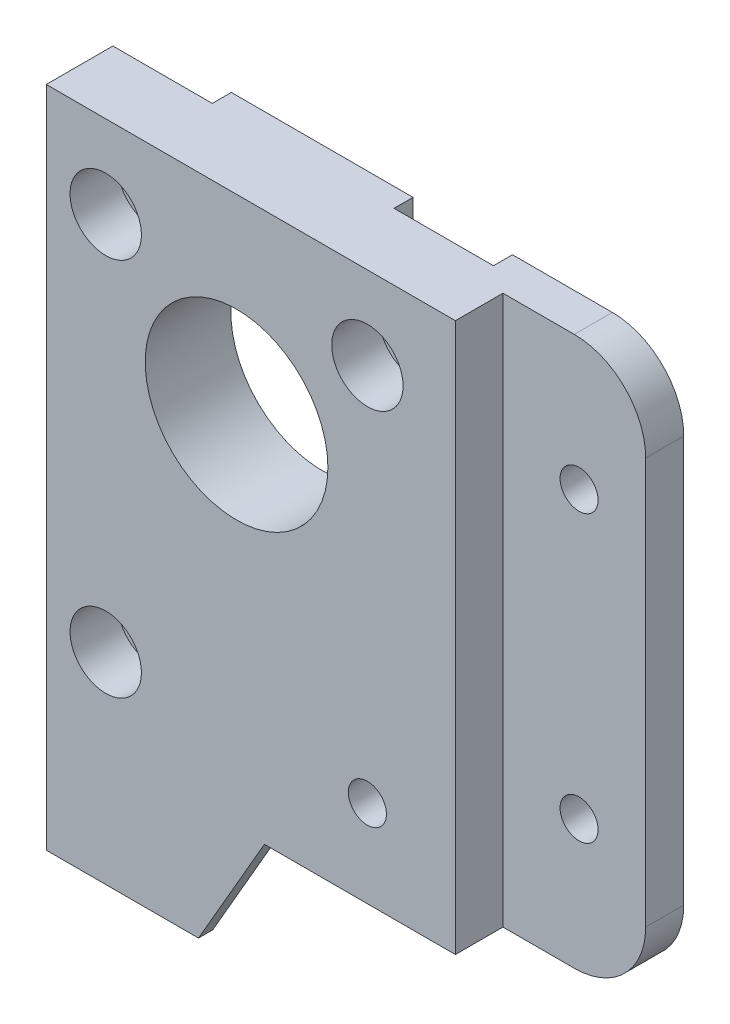
SolidWorks part; units mm, degrees
material "Custom Plastic"
ref_plane "Front Plane" through (0, 0, 0) normal (0, 0, 1) x (1, 0, 0)
ref_plane "Top Plane" through (0, 0, 0) normal (0, 1, 0) x (1, 0, 0)
ref_plane "Right Plane" through (0, 0, 0) normal (1, 0, 0) x (0, 0, -1)
sketch "Sketch1" plane through (0, 0, 0) normal (0, 0, 1) x (1, 0, 0)
  line L0 (-13.75, -19.7) -> (-9.788, -16.65) construction
  line L3 (20, 28.85) -> (38, 28.85)
  line L8 (20, -28.85) -> (-20, -28.85)
  line L9 (20, -28.85) -> (20, 28.85) construction
  line L10 (38, 28.85) -> (38, -28.85)
  line L11 (20, 28.85) -> (-20, 28.85)
  line L14 (-20, -28.85) -> (-20, 28.85)
  line L15 (20, -28.85) -> (-20, 28.85) construction
  line L16 (20, 28.85) -> (-20, -28.85) construction
  line L17 (-16.312, -16.3719) -> (-12.35, -13.3219)
  line L18 (-11.188, -23.0281) -> (-7.226, -19.9781)
  line L19 (0, -28.85) -> (0, 28.85) construction
  line L22 (38, -28.85) -> (20, -28.85)
  line L23 (17.2017, -17.3071) -> (20, -21.3437)
  line L24 (9.55, -19.7) -> (9.55, -28.85)
  line L25 (-9.55, 20.15) -> (-9.55, 28.85)
  line L26 (-17.2017, 17.7571) -> (-20, 21.7937)
  line L27 (9.55, 20.15) -> (9.55, 28.85)
  line L28 (17.2017, 17.7571) -> (20, 21.7937)
  line L29 (20, 21.7937) -> (20, 28.85)
  line L30 (-16.312, -16.3719) -> (-20, -16.3719)
  line L31 (20, -28.85) -> (20, -21.3437)
  line L33 (-13.75, -23.9) -> (-13.75, -28.85)
  circle A18 centre (-13.75, 20.15) radius 4.2
  circle A19 centre (13.75, 20.15) radius 4.2
  circle A20 centre (13.75, -19.7) radius 4.2
  arc A21 (-16.312, -16.3719) -> (-11.188, -23.0281) centre (-13.75, -19.7) ccw
  arc A22 (-7.226, -19.9781) -> (-12.35, -13.3219) centre (-9.788, -16.65) ccw
  circle A23 centre (0, 8.8) radius 9.6
  circle A24 centre (-5.725, -6.1) radius 4.2
  circle A25 centre (5.725, -6.1) radius 4.2
  point P0 (0, 0)
  point P14 (-6.4599, -14.088)
  point P31 (-11.769, -18.175)
  point P37 (5.725, -10.3)
  point P40 (0, 0)
  point P43 (20, 28.85)
  point P45 (0, 0)
  point P46 (-20, 28.85)
  point P48 (0, 0)
  point P49 (0, 0)
  dimension "D1" = 57.7
  dimension "D2" = 40
  dimension "D3" = 12.2
  dimension "D4" = 8.4
  dimension "D5" = 8.4
  dimension "D6" = 19.2
  dimension "D7" = 9.15
  dimension "D8" = 27.5
  dimension "D9" = 39.85
  dimension "D10" = 5
  dimension "D12" = 20.05
  dimension "D13" = 11.45
  dimension "D14" = 22.75
  dimension "D15" = 18
extrude "Boss-Extrude1" add sketch "Sketch1" along normal blind 2 contours L11 L14 L8 L9 A25 A24 A23 A22 L18 A21 L17 A20 A19 A18 region at (12.4683, -0.6196, 0)
sketch "Sketch4" plane through (0, 0, 2) normal (0, 0, 1) x (1, 0, 0)
  line L0 (0, -28.85) -> (0, 29) construction
  line L6 (38, -28.85) -> (20, -28.85) construction
  line L8 (-20, -28.85) -> (38, -28.85)
  line L11 (38, -28.85) -> (38, 28.85)
  line L12 (-20, 28.85) -> (-20, -28.85)
  line L13 (-20, -16.3719) -> (-20, 21.7937) construction
  line L14 (-20, 28.85) -> (38, 28.85)
  line L15 (20, 28.85) -> (38, 28.85) construction
  line L16 (38, 28.85) -> (38, -28.85) construction
  circle A2 centre (13.75, -19.7) radius 2
  circle A3 centre (-13.75, 20.15) radius 2
  circle A4 centre (13.75, 20.15) radius 2
  circle A10 centre (-13.75, -19.7) radius 2
  circle A11 centre (0, 8.8) radius 9.6
  circle A12 centre (0, 8.8) radius 9.6 construction
  dimension "D1" = 4
extrude "Boss-Extrude3" add sketch "Sketch4" along normal blind 2
sketch "Sketch5" plane through (0, 0, 4) normal (0, 0, 1) x (1, 0, 0)
  line L0 (-20, 0) -> (38, 0) construction
  line L3 (-20, 28.85) -> (-20, -28.85) construction
  line L4 (38, -28.85) -> (38, 28.85) construction
  circle A0 centre (31, 15) radius 2
  circle A1 centre (31, -15) radius 2
  dimension "D1" = 4
  dimension "D2" = 15
  dimension "D3" = 51
extrude "Cut-Extrude1" cut sketch "Sketch5" against normal blind 4
ref_plane "Plane1" through (0, 0, 0) normal (0, 0, -1) x (-1, 0, 0)
sketch "Sketch6" plane through (0, 0, 4) normal (0, 0, 1) x (1, 0, 0)
  line L0 (23, 28.85) -> (23, -28.85)
  line L1 (38, 28.85) -> (-20, 28.85) construction
  line L2 (-20, -28.85) -> (38, -28.85) construction
  line L3 (38, -28.85) -> (38, 28.85) construction
  circle A52 centre (-13.75, 20.15) radius 3.75
  circle A53 centre (13.75, 20.15) radius 3.75
  circle A54 centre (31, 15) radius 2
  circle A55 centre (13.75, -19.7) radius 3.75
  circle A56 centre (-13.75, -19.7) radius 3.75
  circle A57 centre (31, -15) radius 2
  circle A59 centre (31, 15) radius 2 construction
  circle A60 centre (31, -15) radius 2 construction
  line M5 (-20, 28.85) -> (-20, -28.85)
  line M6 (-20, -28.85) -> (38, -28.85)
  line M7 (38, -28.85) -> (38, 28.85)
  line M8 (38, 28.85) -> (-20, 28.85)
  circle M9 centre (13.75, -19.7) radius 2
  circle M11 centre (0, 8.8) radius 9.6
  dimension "D1" = 7.5
  dimension "D2" = 15
extrude "Boss-Extrude4" add sketch "Sketch6" along normal blind 5 contours A57 A56 A55 A54 A53 A52 M8 M5 M6 M7 M11 | A55 M9 region at (1.8471, -1.2843, 4) region at (10.1061, -19.7, 4)
sketch "Sketch7" plane through (0, 0, 4) normal (0, 0, 1) x (1, 0, 0)
  line L0 (38, -28.85) -> (38, 28.85) construction
  line L1 (30.5, 28.85) -> (38, 28.85)
  line L2 (38, 28.85) -> (38, 21.35)
  line L3 (-20, 0) -> (38, 0) construction
  line L4 (-20, 28.85) -> (-20, -28.85) construction
  line L5 (38, -28.85) -> (38, -21.35)
  line L6 (30.5, -28.85) -> (38, -28.85)
  arc A0 (38, 21.35) -> (30.5, 28.85) centre (30.5, 21.35) ccw
  arc A1 (38, -21.35) -> (30.5, -28.85) centre (30.5, -21.35) cw
  dimension "D1" = 15
extrude "Cut-Extrude2" cut sketch "Sketch7" against normal through all
sketch "Sketch9" plane through (-20, 0, 0) normal (-1, 0, 0) x (0, 0, 1)
  line L0 (9, -28.85) -> (9, -40.85)
  line L2 (9, -40.85) -> (0, -40.85)
  line L3 (0, -40.85) -> (0, -35.15)
  line L4 (0, -35.15) -> (3, -35.15)
  line L5 (3, -35.15) -> (3, -28.85)
  line L6 (9, -28.85) -> (2, -28.85) construction
  line L7 (0, -16.3719) -> (0, 21.7937) construction
  line L9 (3, -28.85) -> (9, -28.85)
  dimension "D1" = 6
  dimension "D2" = 12
  dimension "D3" = 6.3
extrude "Boss-Extrude5" add sketch "Sketch9" against normal blind 6
sketch "Sketch10" plane through (0, 0, 9) normal (0, 0, 1) x (1, 0, 0)
  line L0 (-14, -40.85) -> (-4, -40.85)
  line L1 (-4, -40.85) -> (2.9282, -28.85)
  line L3 (2.9282, -28.85) -> (-14, -28.85)
  line L4 (-14, -28.85) -> (-14, -40.85)
  dimension "D1" = 10
  dimension "D2" = 120
extrude "Boss-Extrude6" add sketch "Sketch10" against normal blind 1.5
